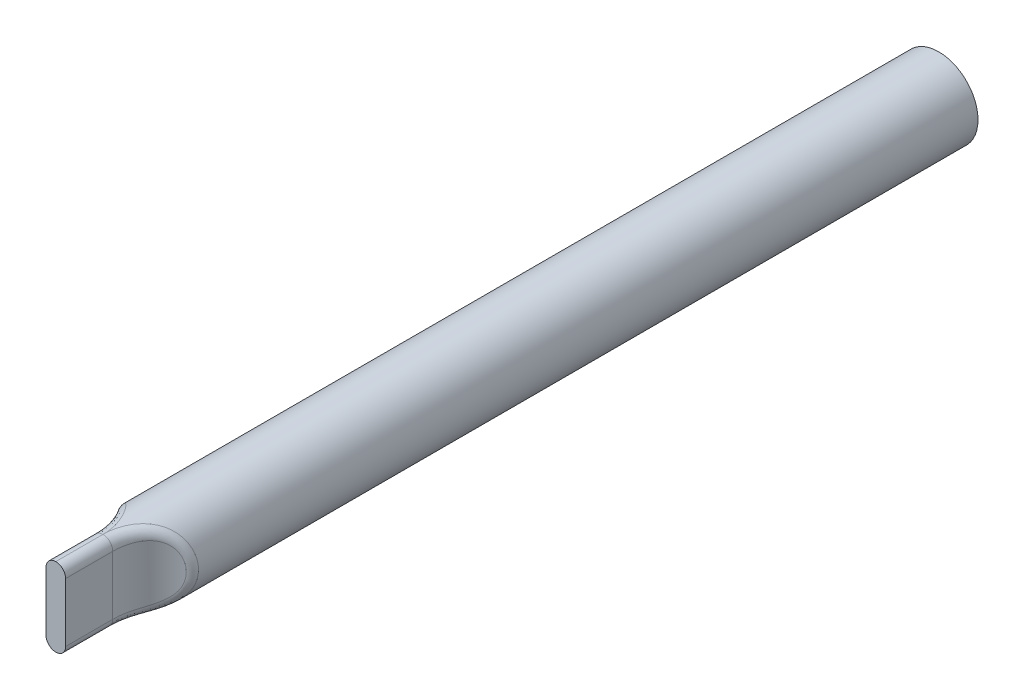
SolidWorks part; units mm, degrees
ref_plane "Front Plane" through (0, 0, 0) normal (0, 0, 1) x (1, 0, 0)
ref_plane "Top Plane" through (0, 0, 0) normal (0, 1, 0) x (1, 0, 0)
ref_plane "Right Plane" through (0, 0, 0) normal (1, 0, 0) x (0, 0, -1)
sketch "Sketch1" plane through (0, 0, 0) normal (0, 0, 1) x (1, 0, 0)
  circle A0 centre (0, 0) radius 2
  dimension "D1" = 4
extrude "Boss-Extrude1" add sketch "Sketch1" along normal blind 45
sketch "Sketch2" plane through (0, 0, 0) normal (0, 1, 0) x (1, 0, 0)
  line L0 (0, -45) -> (0, -25.1492) construction
  line L1 (-2, -45) -> (2, -45) construction
  line L2 (-0.5, -45) -> (-0.5, -42.5981)
  line L3 (-2, 0) -> (-2, -45) construction
  line L4 (-2, -40) -> (-2, -45)
  line L5 (-2, -45) -> (-0.5, -45)
  line L6 (2, -45) -> (0.5, -45)
  line L7 (2, -40) -> (2, -45)
  line L8 (0.5, -45) -> (0.5, -42.5981)
  arc A0 (-0.5, -42.5981) -> (-2, -40) centre (-3.5, -42.5981) ccw
  arc A1 (0.5, -42.5981) -> (2, -40) centre (3.5, -42.5981) cw
  dimension "D2" = 3
  dimension "D1" = 1
  dimension "D3" = 5
extrude "Cut-Extrude1" cut sketch "Sketch2" against normal through all both and the other way through all
fillet "Fillet1" radius 0.5 6 edges at (0.5, -1.9365, 43.799) (1.9982, -0.0842, 40.001) (-0.5, -1.9365, 43.799) (-0.5, 1.9365, 43.799) (0.5, 1.9365, 43.799) (-1.9982, 0.0842, 40.001)
shell "Shell1" thickness 0.25 removed face at (2, 0, 0)
sketch "Sketch3" plane through (0, 0, 0) normal (0, 1, 0) x (1, 0, 0)
  line L0 (0, 0) -> (0, -24) construction
  line L1 (0, -24) -> (0, -29) construction
  line L2 (0, -29) -> (0, -34) construction
  line L3 (-0.5, -45) -> (0, -45) construction
  circle A0 centre (0, -34) radius 1
  circle A1 centre (0, -29) radius 1
  circle A2 centre (0, -24) radius 1
  dimension "D1" = 2
  dimension "D3" = 11
  dimension "D2" = 5
extrude "Cut-Extrude2" cut sketch "Sketch3" against normal blind 30
sketch "Sketch4" plane through (0, 0, 0) normal (0, 1, 0) x (0, 0, -1)
  line L0 (8, 20) -> (8, 8)
  arc A0 (8, 8) -> (0, 0) centre (0, 8) cw
  dimension "D2" = 8
  dimension "D1" = 20
sweep "Sweep-Thin1" [suppressed] add path "Sketch4" circular profile diameter 4 parameters "D1"=0.25, "D3"=4
sketch "Sketch5" plane through (0, 0, 45) normal (0, 0, 1) x (1, 0, 0)
  line L0 (0, 0) -> (0, -23)
  dimension "D1" = 23
